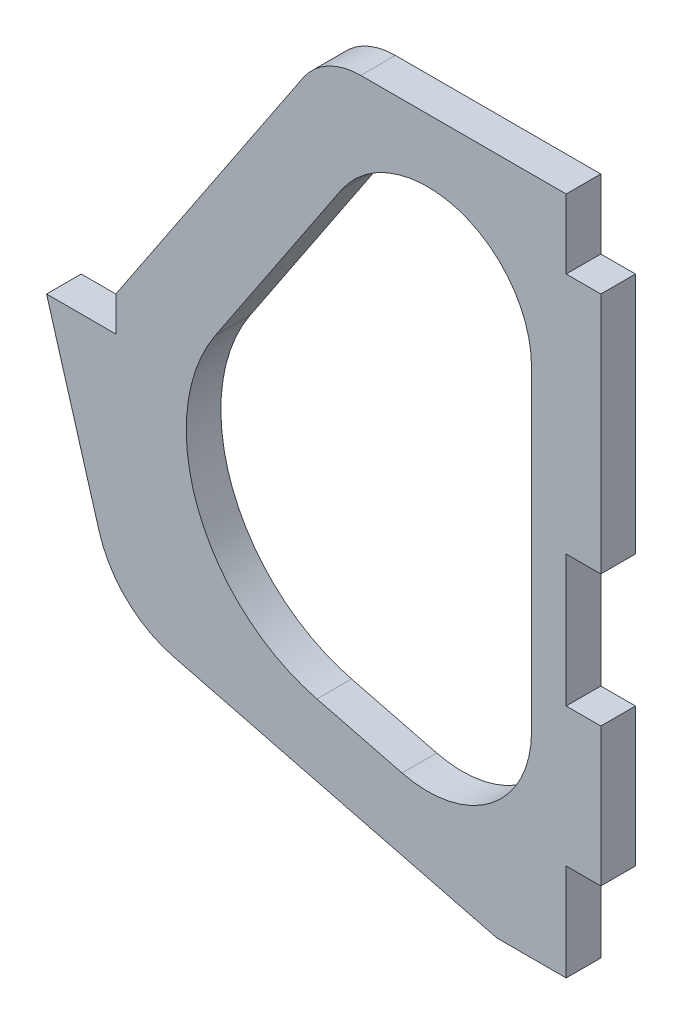
SolidWorks part; units mm, degrees
material "Stal węglowa"
ref_plane "Front" through (0, 0, 0) normal (0, 0, 1) x (1, 0, 0)
ref_plane "Top" through (0, 0, 0) normal (0, 1, 0) x (1, 0, 0)
ref_plane "Right" through (0, 0, 0) normal (1, 0, 0) x (0, 0, -1)
sketch "Szkic1" plane through (0, 0, 0) normal (0, 0, 1) x (1, 0, 0)
  line L209 (9.7229, -5.8852) -> (14.7229, -5.8852)
  line L210 (14.7229, -5.8852) -> (14.7229, -25.8852)
  line L211 (14.7229, -25.8852) -> (9.7229, -25.8852)
  line L212 (9.7229, -25.8852) -> (9.7229, -39.8852)
  line L213 (9.7229, -39.8852) -> (-0.2771, -39.8852)
  line L214 (-19.9252, 58.1148) -> (9.7229, 58.1148)
  line L215 (9.7229, -5.8852) -> (9.7229, 13.1148)
  line L216 (-0.2771, -39.8852) -> (-46.979, -28.054)
  line L217 (-55.2771, 13.1148) -> (-55.2771, 8.1148)
  line L218 (14.7229, 13.1148) -> (14.7229, 48.1148)
  line L219 (14.7229, 13.1148) -> (9.7229, 13.1148)
  line L220 (9.7229, 48.1148) -> (14.7229, 48.1148)
  line L221 (9.7229, 58.1148) -> (9.7229, 48.1148)
  line L222 (-28.2457, 53.6618) -> (-55.2771, 13.1148)
  line L223 (-65.2771, 8.1148) -> (-55.2771, 8.1148)
  line L224 (-65.2771, 8.1148) -> (-57.6881, -17.7382)
  line L225 (4.7229, 34.0316) -> (4.7229, -11.5621)
  line L226 (-13.9607, -26.1028) -> (-26.2549, -22.9882)
  line L227 (-22.7578, 42.3521) -> (-40.9167, 15.1137)
  arc A86 (-19.9252, 58.1148) -> (-28.2457, 53.6618) centre (-19.9252, 48.1148) ccw
  arc A87 (-57.6881, -17.7382) -> (-46.979, -28.054) centre (-43.2954, -13.5134) ccw
  arc A88 (-40.9167, 15.1137) -> (-26.2549, -22.9882) centre (-20.1155, 1.2462) ccw
  arc A89 (4.7229, 34.0316) -> (-22.7578, 42.3521) centre (-10.2771, 34.0316) ccw
  arc A90 (-13.9607, -26.1028) -> (4.7229, -11.5621) centre (-10.2771, -11.5621) ccw
extrude "Dodanie-wyciągnięcie1" add sketch "Szkic1" along normal blind 5
